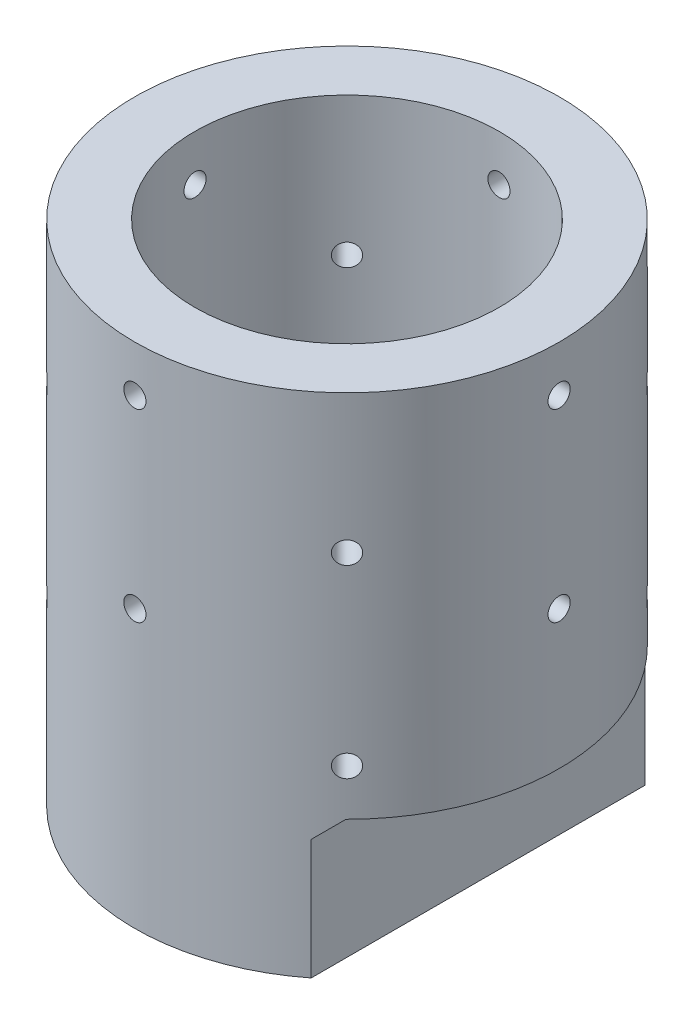
SolidWorks part; units mm, degrees
ref_plane "Спереди" through (0, 0, 0) normal (0, 0, 1) x (1, 0, 0)
ref_plane "Сверху" through (0, 0, 0) normal (0, 1, 0) x (1, 0, 0)
ref_plane "Справа" through (0, 0, 0) normal (1, 0, 0) x (0, 0, -1)
sketch "Эскиз1" plane through (0, 0, 0) normal (0, 1, 0) x (1, 0, 0)
  circle A0 centre (0, 0) radius 23
  dimension "D1" = 46
extrude "Бобышка-Вытянуть1" add sketch "Эскиз1" along normal blind 5
sketch "Эскиз2" plane through (0, 5, 0) normal (0, 1, 0) x (1, 0, 0)
  circle A0 centre (0, 0) radius 23
  circle A1 centre (0, 0) radius 16.5
  circle A2 centre (0, 0) radius 23 construction
  dimension "D1" = 33
  dimension "D2" = 0
extrude "Бобышка-Вытянуть2" add sketch "Эскиз2" along normal blind 35
chamfer "Фаска8" distance 2 angle 45 1 edges at (0, 5, 16.5)
sketch "Эскиз3" plane through (0, 0, 0) normal (1, 0, 0) x (0, 0, -1)
  line L0 (-23, 20) -> (28.0263, 20) construction
  line L1 (-23, 40) -> (-23, 0) construction
  line L2 (16.5, 40) -> (-16.5, 40) construction
  circle A1 centre (0, 35) radius 1.2
  dimension "D1" = 2.4
  dimension "D2" = 5
extrude "Вырез-Вытянуть1" cut sketch "Эскиз3" against normal through all
ref_plane "Плоскость1" through (0, 0, 0) normal (0.7071, 0, 0.7071) x (0, -1, 0)
sketch "Эскиз4" plane through (0, 0, 0) normal (0.7071, 0, 0.7071) x (0, -1, 0)
  line L0 (-20, 23) -> (-20, -30.0625) construction
  line L1 (0, 23) -> (-40, 23) construction
  line L3 (0, -23) -> (0, 23) construction
  circle A1 centre (-5, 0) radius 1.2
  dimension "D1" = 5
  dimension "D2" = 2.4
extrude "Вырез-Вытянуть2" cut sketch "Эскиз4" against normal through all from offset 16.3 offset against normal yes
pattern_circular "Круговой массив1" count 4 over 360 about axis through (0, 5, 0) along (0, -1, 0) of "Вырез-Вытянуть2"
pattern_circular "Круговой массив2" count 4 over 360 about axis through (0, 5, 0) along (0, -1, 0) of "Вырез-Вытянуть1"
pattern_linear "Линейный массив3" count 2 spacing 20 along (0, 1, 0) of "Круговой массив1"
pattern_linear "Линейный массив4" count 2 spacing 20 along (0, -1, 0) of "Круговой массив2"
sketch "Эскиз12" plane through (0, 0, 0) normal (0, -1, 0) x (1, 0, 0)
  line L1 (14.207, 18.0876) -> (14.207, -18.0876)
  line L20 (0, 15) -> (-2.7835, 17.7835)
  line L21 (-2.7835, -17.7835) -> (0, -15)
  line L22 (0, -15) -> (0, 15)
  line L23 (0, 15) -> (-2.7835, 17.7835)
  line L24 (-2.7835, -17.7835) -> (0, -15)
  line L25 (0, -15) -> (0, 15)
  circle A6 centre (0, 0) radius 23 construction
  arc A7 (14.207, 18.0876) -> (14.207, -18.0876) centre (0, 0) ccw
  arc A13 (-2.7835, 17.7835) -> (-2.7835, -17.7835) centre (0, 0) ccw
  arc A14 (-2.7835, 17.7835) -> (-2.7835, -17.7835) centre (0, 0) ccw
  point P9 (0, 0)
  dimension "D1" = 0
extrude "Бобышка-Вытянуть3" add sketch "Эскиз12" along normal blind 15 contours L1 region at (13.6153, 0, 0)
sketch "Эскиз13" plane through (0, -15, 0) normal (0, -1, 0) x (1, 0, 0)
  line L14 (-2.6786, -18.1029) -> (0.3, -15.1243)
  line L15 (0.3, 15.1243) -> (-2.6786, 18.1029)
  line L16 (0.3, -15.1243) -> (0.3, 15.1243)
  line L17 (-2.6786, -18.1029) -> (0.3, -15.1243)
  line L18 (0.3, 15.1243) -> (-2.6786, 18.1029)
  line L19 (0.3, -15.1243) -> (0.3, 15.1243)
  arc A5 (-2.6786, 18.1029) -> (-2.6786, -18.1029) centre (0, 0) ccw
  arc A6 (-2.6786, 18.1029) -> (-2.6786, -18.1029) centre (0, 0) ccw
  dimension "D1" = 0.3
extrude "Вырез-Вытянуть10" cut sketch "Эскиз13" against normal up to surface (15 mm away) up to face at (18.6035, 0, 0)
chamfer "Фаска4" distance 2 angle 45 1 edges at (14.207, 0, 0)
chamfer "Фаска6" distance 2 angle 45 4 edges at (-1.1893, 0, -16.6136) (-18.3, 0, 0) (0.3, 0, 0) (-1.1893, 0, 16.6136)
chamfer "Фаска7" distance 2 angle 45 4 edges at (-1.1893, -15, -16.6136) (-18.3, -15, 0) (-1.1893, -15, 16.6136) (0.3, -15, 0)
